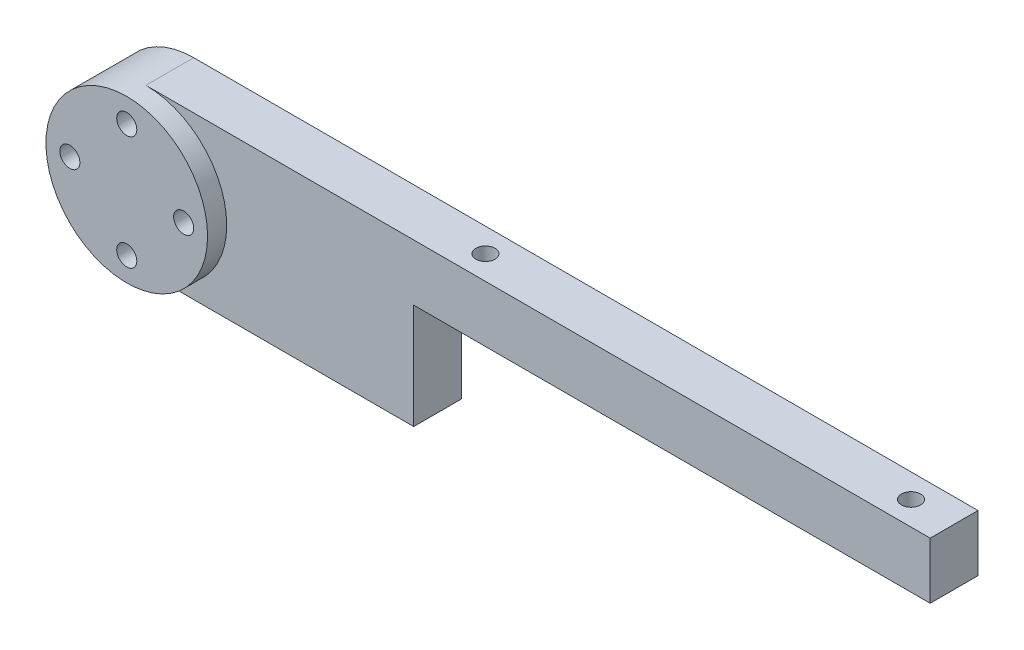
SolidWorks part; units mm, degrees
ref_plane "정면" through (0, 0, 0) normal (0, 0, 1) x (1, 0, 0)
ref_plane "윗면" through (0, 0, 0) normal (0, 1, 0) x (1, 0, 0)
ref_plane "우측면" through (0, 0, 0) normal (1, 0, 0) x (0, 0, -1)
sketch "스케치1" plane through (0, 0, 0) normal (0, 0, 1) x (1, 0, 0)
  line L0 (0, 8.45) -> (110, 8.45)
  line L1 (110, 8.45) -> (110, -8.45)
  line L2 (110, -8.45) -> (0, -8.45)
  line L4 (110, 8.45) -> (30, 8.45) construction
  line L5 (110, 8.45) -> (110, -8.45) construction
  line L6 (110, -8.45) -> (30, -8.45) construction
  line L7 (30, 8.45) -> (30, -8.45) construction
  arc A0 (0, 8.45) -> (0, -8.45) centre (0, 0) ccw
  circle A1 centre (0, 0) radius 5.95 construction
  circle A2 centre (-5.95, 0) radius 1.05
  circle A3 centre (0, 5.95) radius 1.05
  circle A4 centre (5.95, 0) radius 1.05
  circle A5 centre (0, -5.95) radius 1.05
  dimension "D1" = 16.9
  dimension "D4" = 2.5
  dimension "D5" = 2.1
  dimension "D2" = 80
  dimension "D3" = 30
extrude "보스-돌출1" add sketch "스케치1" along normal blind 2.5
sketch "스케치2" plane through (0, 0, 0) normal (0, 0, -1) x (-1, 0, 0)
  line L2 (-110, -8.45) -> (-28, -8.45)
  line L3 (-110, -8.45) -> (-110, -1.45)
  line L4 (-110, -1.45) -> (-28, -1.45)
  line L7 (-28, -8.45) -> (-28, -1.45)
  dimension "D1" = 7
  dimension "D2" = 82
extrude "컷-돌출1" cut sketch "스케치2" against normal blind 2.5
sketch "스케치3" plane through (0, 0, 0) normal (0, 0, -1) x (-1, 0, 0)
  line L1 (-107, 2.55) -> (-28, 2.55)
  line L2 (-107, 2.55) -> (-107, -1.45)
  line L3 (-107, -1.45) -> (-28, -1.45)
  line L4 (-28, 2.55) -> (-28, -1.45)
  dimension "D1" = 4
extrude "보스-돌출2" add sketch "스케치3" along normal blind 10.7
sketch "스케치4" plane through (0, -1.45, 0) normal (0, -1, 0) x (1, 0, 0)
  line L0 (28, -10.7) -> (107, -10.7) construction
  line L1 (67.5, -10.7) -> (67.5, 2.5) construction
  line L2 (28, 2.5) -> (110, 2.5) construction
  line L3 (73.899, -10.7) -> (74.301, -10.7)
  line L4 (67.299, -10.7) -> (67.701, -10.7)
  line L5 (67.299, -10.7) -> (67.299, 2.5)
  line L6 (67.299, 2.5) -> (67.701, 2.5)
  line L7 (67.701, -10.7) -> (67.701, 2.5)
  line L8 (67.299, -10.7) -> (67.701, 2.5) construction
  line L9 (67.299, 2.5) -> (67.701, -10.7) construction
  line L10 (73.899, -10.7) -> (73.899, 2.5)
  line L11 (73.899, 2.5) -> (74.301, 2.5)
  line L12 (74.301, -10.7) -> (74.301, 2.5)
  line L13 (34.6, -10.7) -> (113.6, -10.7) construction
  line L14 (74.1, -10.7) -> (74.1, 2.5) construction
  line L15 (73.899, -10.7) -> (74.301, 2.5) construction
  line L16 (73.899, 2.5) -> (74.301, -10.7) construction
  line L17 (80.499, -10.7) -> (80.901, -10.7)
  line L18 (80.499, -10.7) -> (80.499, 2.5)
  line L19 (80.499, 2.5) -> (80.901, 2.5)
  line L20 (80.901, -10.7) -> (80.901, 2.5)
  line L21 (41.2, -10.7) -> (120.2, -10.7) construction
  line L22 (80.7, -10.7) -> (80.7, 2.5) construction
  line L23 (80.499, -10.7) -> (80.901, 2.5) construction
  line L24 (80.499, 2.5) -> (80.901, -10.7) construction
  line L25 (87.099, -10.7) -> (87.501, -10.7)
  line L26 (87.099, -10.7) -> (87.099, 2.5)
  line L27 (87.099, 2.5) -> (87.501, 2.5)
  line L28 (87.501, -10.7) -> (87.501, 2.5)
  line L29 (47.8, -10.7) -> (126.8, -10.7) construction
  line L30 (87.3, -10.7) -> (87.3, 2.5) construction
  line L31 (87.099, -10.7) -> (87.501, 2.5) construction
  line L32 (87.099, 2.5) -> (87.501, -10.7) construction
  line L33 (93.699, -10.7) -> (94.101, -10.7)
  line L34 (93.699, -10.7) -> (93.699, 2.5)
  line L35 (93.699, 2.5) -> (94.101, 2.5)
  line L36 (94.101, -10.7) -> (94.101, 2.5)
  line L37 (54.4, -10.7) -> (133.4, -10.7) construction
  line L38 (93.9, -10.7) -> (93.9, 2.5) construction
  line L39 (93.699, -10.7) -> (94.101, 2.5) construction
  line L40 (93.699, 2.5) -> (94.101, -10.7) construction
  point P8 (67.5, -4.1)
  point P19 (74.1, -4.1)
  point P28 (80.7, -4.1)
  point P37 (87.3, -4.1)
  point P44 (93.9, -4.1)
  dimension "D1" = 5
extrude "보스-돌출3" add sketch "스케치4" along normal blind 0.6
sketch "스케치5" plane through (0, -1.45, 0) normal (0, -1, 0) x (1, 0, 0)
  line L0 (70.8, 2.5) -> (70.8, -10.7) construction
  line L1 (67.701, 2.5) -> (73.899, 2.5) construction
  line L2 (73.899, -10.7) -> (67.701, -10.7) construction
  line L3 (70.8, -8.95) -> (70.8, 0.75) construction
  line L4 (67.701, -10.7) -> (67.701, 2.5) construction
  line L5 (67.701, 0.75) -> (73.899, 0.75)
  line L6 (67.701, 0.75) -> (67.701, 1.15)
  line L7 (67.701, 1.15) -> (73.899, 1.15)
  line L8 (73.899, 0.75) -> (73.899, 1.15)
  line L9 (73.899, 2.5) -> (73.899, -10.7) construction
  line L10 (70.8, -4.1) -> (73.899, -4.1) construction
  line L11 (73.899, -8.95) -> (73.899, -9.35)
  line L12 (67.701, -9.35) -> (73.899, -9.35)
  line L13 (67.701, -8.95) -> (67.701, -9.35)
  line L14 (67.701, -8.95) -> (73.899, -8.95)
  line L15 (74.301, 0.75) -> (80.499, 0.75)
  line L16 (74.301, 0.75) -> (74.301, 1.15)
  line L17 (74.301, 1.15) -> (80.499, 1.15)
  line L18 (80.499, 0.75) -> (80.499, 1.15)
  line L19 (80.499, -8.95) -> (80.499, -9.35)
  line L20 (74.301, -9.35) -> (80.499, -9.35)
  line L21 (74.301, -8.95) -> (74.301, -9.35)
  line L22 (74.301, -8.95) -> (80.499, -8.95)
  line L23 (77.4, 2.5) -> (77.4, -10.7) construction
  line L24 (77.4, -8.95) -> (77.4, 0.75) construction
  line L25 (77.4, -4.1) -> (80.499, -4.1) construction
  line L26 (80.901, 0.75) -> (87.099, 0.75)
  line L27 (80.901, 0.75) -> (80.901, 1.15)
  line L28 (80.901, 1.15) -> (87.099, 1.15)
  line L29 (87.099, 0.75) -> (87.099, 1.15)
  line L30 (87.099, -8.95) -> (87.099, -9.35)
  line L31 (80.901, -9.35) -> (87.099, -9.35)
  line L32 (80.901, -8.95) -> (80.901, -9.35)
  line L33 (80.901, -8.95) -> (87.099, -8.95)
  line L34 (84, 2.5) -> (84, -10.7) construction
  line L35 (84, -8.95) -> (84, 0.75) construction
  line L36 (84, -4.1) -> (87.099, -4.1) construction
  line L37 (87.501, 0.75) -> (93.699, 0.75)
  line L38 (87.501, 0.75) -> (87.501, 1.15)
  line L39 (87.501, 1.15) -> (93.699, 1.15)
  line L40 (93.699, 0.75) -> (93.699, 1.15)
  line L41 (93.699, -8.95) -> (93.699, -9.35)
  line L42 (87.501, -9.35) -> (93.699, -9.35)
  line L43 (87.501, -8.95) -> (87.501, -9.35)
  line L44 (87.501, -8.95) -> (93.699, -8.95)
  line L45 (90.6, 2.5) -> (90.6, -10.7) construction
  line L46 (90.6, -8.95) -> (90.6, 0.75) construction
  line L47 (90.6, -4.1) -> (93.699, -4.1) construction
  dimension "D1" = 4
extrude "보스-돌출4" add sketch "스케치5" along normal blind 0.4
sketch "스케치6" plane through (0, 0, -10.7) normal (0, 0, -1) x (-1, 0, 0)
  line L1 (-28, 2.55) -> (-107, 2.55)
  line L2 (-28, 2.55) -> (-28, -4.167)
  line L3 (-28, -4.167) -> (-107, -4.167)
  line L4 (-107, 2.55) -> (-107, -4.167)
extrude "컷-돌출2" cut sketch "스케치6" against normal blind 20
sketch "스케치7" plane through (0, 0, 0) normal (0, 0, -1) x (-1, 0, 0)
  line L0 (-107, -1.45) -> (-110, -1.45)
  line L1 (-110, -1.45) -> (-110, 8.45)
  line L2 (-110, 8.45) -> (0, 8.45)
  line L3 (-110, 8.45) -> (0, 8.45) construction
  line L4 (0, -8.45) -> (-28, -8.45) construction
  line L5 (0, -8.45) -> (-28, -8.45)
  line L6 (-28, -8.45) -> (-28, 2.55)
  line L7 (-28, 2.55) -> (-107, 2.55)
  line L8 (-107, 2.55) -> (-107, -1.45)
  arc A0 (0, -8.45) -> (0, 8.45) centre (0, 0) ccw construction
  arc A1 (1.7749, 8.2615) -> (0, -8.45) centre (0, 0) cw
  circle A2 centre (5.95, 0) radius 1
  circle A3 centre (0, -5.95) radius 1
  circle A4 centre (-5.95, 0) radius 1
  circle A5 centre (0, 5.95) radius 1
  circle M1 centre (0, -5.95) radius 1.05
  circle M2 centre (-5.95, 0) radius 1.05
  circle M3 centre (0, 5.95) radius 1.05
  circle M4 centre (5.95, 0) radius 1.05
  line M5 (-107, -1.45) -> (-107, 2.55)
  line M6 (-107, 2.55) -> (-28, 2.55)
  line M7 (-28, 2.55) -> (-28, -8.45)
  line M8 (-28, -8.45) -> (0, -8.45)
  arc M9 (0, -8.45) -> (0, 8.45) centre (0, 0) ccw
  line M10 (0, 8.45) -> (-110, 8.45)
  line M11 (-110, 8.45) -> (-110, -1.45)
  line M12 (-110, -1.45) -> (-107, -1.45)
extrude "보스-돌출5" add sketch "스케치7" along normal blind 2.5 contours M12 M5 M6 M7 M8 M9 M10 M11 M2 M4 M3 M1 region at (108.5, -0.2535, 0)
sketch "스케치9" plane through (0, 2.55, 0) normal (0, -1, 0) x (1, 0, 0)
  line L0 (107, 0) -> (102, 0) construction
  line L1 (107, 2.5) -> (107, -2.5) construction
  line L2 (28, 0) -> (33, 0) construction
  line L3 (28, 2.5) -> (28, -2.5) construction
  circle A0 centre (102, 0) radius 1
  circle A1 centre (33, 0) radius 1
  dimension "D1" = 5
  dimension "D2" = 5
extrude "컷-돌출3" cut sketch "스케치9" against normal blind 10
sketch "스케치10" plane through (0, 2.55, 0) normal (0, -1, 0) x (1, 0, 0)
  circle A0 centre (77.5, 0) radius 1
  circle A1 centre (33, 0) radius 1 construction
  dimension "D1" = 44.5
extrude "컷-돌출4" cut sketch "스케치10" against normal blind 10
sketch "스케치11" plane through (110, 0, 0) normal (1, 0, 0) x (0, 0, -1)
  line L1 (2.5, 8.45) -> (-2.5, 8.45)
  line L2 (2.5, 8.45) -> (2.5, -1.45)
  line L3 (2.5, -1.45) -> (-2.5, -1.45)
  line L4 (-2.5, 8.45) -> (-2.5, -1.45)
extrude "컷-돌출5" cut sketch "스케치11" against normal blind 28
sketch "스케치13" plane through (0, 0, 2.5) normal (0, 0, 1) x (1, 0, 0)
  circle A0 centre (0, 0) radius 8.45
  circle A1 centre (0, -5.95) radius 1.05
  circle A2 centre (5.95, 0) radius 1.05
  circle A3 centre (0, 5.95) radius 1.05
  circle A4 centre (-5.95, 0) radius 1.05
extrude "보스-돌출7" add sketch "스케치13" along normal blind 2
